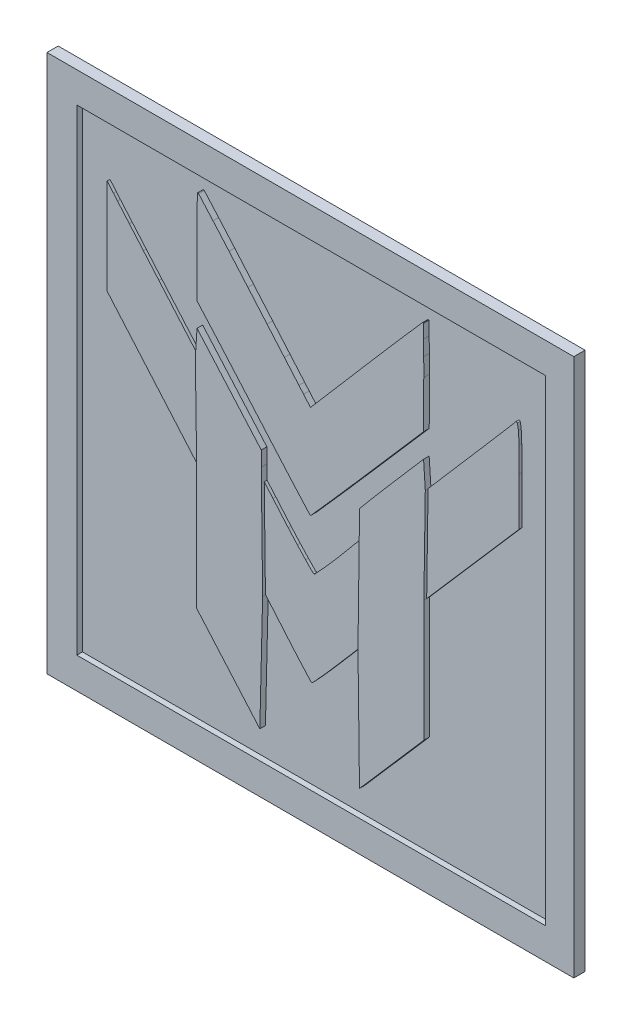
SolidWorks part; units mm, degrees
ref_plane "Front Plane" through (0, 0, 0) normal (0, 0, 1) x (1, 0, 0)
ref_plane "Top Plane" through (0, 0, 0) normal (0, 1, 0) x (1, 0, 0)
ref_plane "Right Plane" through (0, 0, 0) normal (1, 0, 0) x (0, 0, -1)
sketch "Model" plane through (0, 0, 0) normal (0, 0, 1) x (1, 0, 0)
  line L0 (33.0408, 138.25) -> (33.0816, 121.5)
  line L1 (33.0816, 121.5) -> (37.9485, 116)
  line L2 (37.9485, 116) -> (40.7262, 112.8407)
  line L3 (40.7262, 112.8407) -> (45.8443, 106.975)
  line L4 (45.8443, 106.975) -> (51.8256, 100.1032)
  line L5 (51.8256, 100.1032) -> (57.9935, 93)
  line L6 (57.9935, 93) -> (63.8389, 86.2903)
  line L7 (68.8187, 80.6406) -> (73.2898, 75.6085)
  line L8 (73.7744, 75.6093) -> (79.664, 82.2562)
  line L9 (86.2039, 89.6813) -> (93.9024, 98.5)
  line L10 (93.9024, 98.5) -> (113.9132, 121.5)
  line L11 (113.9132, 121.5) -> (113.9566, 138.25)
  line L12 (113.8851, 150.0797) -> (113.7941, 154.8608)
  line L13 (113.4179, 154.8938) -> (107.5701, 148.2145)
  line L14 (101.079, 140.7574) -> (93.4361, 131.9005)
  line L15 (93.4361, 131.9005) -> (73.5679, 108.801)
  line L16 (73.5679, 108.801) -> (71.1065, 111.6505)
  line L17 (71.1065, 111.6505) -> (69.44, 113.5836)
  line L18 (69.44, 113.5836) -> (64.254, 119.6114)
  line L19 (64.254, 119.6114) -> (58.0834, 126.7856)
  line L20 (58.0834, 126.7856) -> (51.2352, 134.75)
  line L21 (51.2352, 134.75) -> (44.5303, 142.5141)
  line L22 (38.8182, 149.0516) -> (33.6892, 154.8751)
  line L23 (33.2445, 154.8359) -> (33.1332, 150.0797)
  line L24 (0.036, 124.5) -> (0.0001, 107.5)
  line L25 (0.0001, 107.5) -> (16.5, 88.3599)
  line L26 (16.5, 88.3599) -> (33, 69.2198)
  line L27 (33, 69.2198) -> (33, 47.8254)
  line L28 (33, 47.8254) -> (33, 26.431)
  line L29 (33, 26.431) -> (44.25, 13.4785)
  line L30 (44.25, 13.4785) -> (55.5, 0.5261)
  line L31 (55.5, 0.5261) -> (56, 21.2648)
  line L32 (56, 21.2648) -> (56.5, 42.0036)
  line L33 (56.5, 42.0036) -> (64.5, 32.5666)
  line L34 (70.2969, 25.8917) -> (72.6749, 23.2531)
  line L35 (73.3274, 23.2256) -> (75.85, 25.9702)
  line L36 (82, 32.9302) -> (90.5, 42.7993)
  line L37 (90.5, 42.7993) -> (90.7697, 21.3399)
  line L38 (90.7697, 21.3399) -> (91.0393, -0.1195)
  line L39 (91.0393, -0.1195) -> (102.5197, 13.0656)
  line L40 (102.5197, 13.0656) -> (114, 26.2506)
  line L41 (114, 26.2506) -> (114.0006, 47.8753)
  line L42 (114.0006, 47.8753) -> (114.0013, 69.5)
  line L43 (114.0013, 69.5) -> (130.5006, 88.4566)
  line L44 (130.5006, 88.4566) -> (147, 107.4132)
  line L45 (147, 107.4132) -> (146.9682, 124.4566)
  line L46 (144.8065, 138.8353) -> (140.4516, 133.7563)
  line L47 (140.4516, 133.7563) -> (135.336, 127.8101)
  line L48 (135.336, 127.8101) -> (129.5, 121.0523)
  line L49 (129.5, 121.0523) -> (114.5, 103.71)
  line L50 (114.5, 103.71) -> (114.1956, 108.3444)
  line L51 (114.1956, 108.3444) -> (113.8913, 112.9787)
  line L52 (113.8913, 112.9787) -> (102.4514, 99.7394)
  line L53 (76.7235, 59.9622) -> (74.2571, 57.2865)
  line L54 (73.382, 57.2298) -> (70.829, 59.8845)
  line L55 (95.0771, 91.1037) -> (91.0033, 86.2762)
  line L56 (33.1107, 113.0274) -> (32.8053, 108.4215)
  line L57 (32.8053, 108.4215) -> (32.5, 103.8157)
  line L58 (32.5, 103.8157) -> (18.5, 120.0291)
  line L59 (18.5, 120.0291) -> (12.9763, 126.4308)
  line L60 (12.9763, 126.4308) -> (7.9621, 132.252)
  line L61 (7.9621, 132.252) -> (3.7607, 137.1379)
  line L62 (3.7607, 137.1379) -> (2.286, 138.8713)
  line L63 (2.286, 138.8713) -> (0.0719, 141.5)
  line L64 (0.0719, 141.5) -> (0.036, 124.5)
  line L65 (33, 69.2198) -> (32.5, 103.8157)
  line L66 (56.5, 42.0036) -> (56.014, 81.5865)
  line L67 (90.5, 42.7993) -> (91.0033, 81.5)
  line L68 (114.0013, 69.5) -> (114.5, 103.71)
  line L69 (33.1107, 113.0274) -> (56.014, 86.8827)
  line L70 (56.014, 86.8827) -> (56.014, 81.5865)
  line L71 (32.5, 103.8157) -> (59.1934, 73.0087) construction
  line L72 (59.1934, 73.0087) -> (56.0752, 76.6075)
  line L73 (91.0033, 86.2762) -> (91.0033, 81.5)
  line L74 (114.5, 103.71) -> (87.8675, 72.9491) construction
  line L75 (87.8675, 72.9491) -> (90.9382, 76.4959)
  line L77 (-20.401, -20.4475) -> (167.4641, -20.4475)
  line L78 (-20.401, -20.4475) -> (-20.401, 171.4475)
  line L79 (-20.401, 171.4475) -> (167.4641, 171.4475)
  line L80 (167.4641, -20.4475) -> (167.4641, 171.4475)
  line L81 (-20.401, -20.4475) -> (167.4641, 171.4475) construction
  line L82 (-20.401, 171.4475) -> (167.4641, -20.4475) construction
  line L83 (157.3002, -9.3509) -> (-9.7514, -9.3509)
  line L84 (157.3002, -9.3509) -> (157.3002, 160.5695)
  line L85 (157.3002, 160.5695) -> (-9.7514, 160.5695)
  line L86 (-9.7514, -9.3509) -> (-9.7514, 160.5695)
  line L87 (157.3002, -9.3509) -> (-9.7514, 160.5695) construction
  line L88 (157.3002, 160.5695) -> (-9.7514, -9.3509) construction
  arc A0 (63.8389, 86.2903) -> (68.8187, 80.6406) centre (848.3924, 772.8169) ccw
  arc A1 (73.2898, 75.6085) -> (73.5315, 75.5) centre (73.5315, 75.8234) ccw
  arc A2 (73.5315, 75.5) -> (73.7744, 75.6093) centre (73.5315, 75.8245) ccw
  arc A3 (79.664, 82.2562) -> (86.2039, 89.6813) centre (-1267.0712, 1275.0405) ccw
  arc A4 (113.9566, 138.25) -> (113.9482, 144.6728) centre (-711.1704, 140.3877) ccw
  arc A5 (113.9482, 144.6728) -> (113.8851, 150.0797) centre (-302.5075, 142.5101) ccw
  arc A6 (113.7941, 154.8608) -> (113.6521, 155) centre (113.6521, 154.858) ccw
  arc A7 (113.6521, 155) -> (113.4179, 154.8938) centre (113.6521, 154.6887) ccw
  arc A8 (107.5701, 148.2145) -> (101.079, 140.7574) centre (1498.7, -1069.2639) ccw
  arc A9 (44.5303, 142.5141) -> (38.8182, 149.0516) centre (-864.7896, -646.2386) ccw
  arc A10 (33.6892, 154.8751) -> (33.4126, 155) centre (33.4126, 154.6313) ccw
  arc A11 (33.4126, 155) -> (33.2445, 154.8359) centre (33.4126, 154.8318) ccw
  arc A12 (33.1332, 150.0797) -> (33.0548, 144.6728) centre (384.2786, 142.2843) ccw
  arc A13 (33.0548, 144.6728) -> (33.0408, 138.25) centre (728.4501, 139.9437) ccw
  arc A14 (64.5, 32.5666) -> (67.6028, 28.9465) centre (399.1481, 316.2569) ccw
  arc A15 (67.6028, 28.9465) -> (70.2969, 25.8917) centre (244.8339, 182.531) ccw
  arc A16 (72.6749, 23.2531) -> (73, 23.0954) centre (73.033, 23.5772) ccw
  arc A17 (73, 23.0954) -> (73.3274, 23.2256) centre (73.0279, 23.5021) ccw
  arc A18 (75.85, 25.9702) -> (78.7054, 29.1492) centre (-93.9268, 181.3349) ccw
  arc A19 (78.7054, 29.1492) -> (82, 32.9302) centre (-247.5154, 316.7328) ccw
  arc A20 (146.9682, 124.4566) -> (146.9051, 133.3026) centre (-692.3329, 122.8912) ccw
  arc A21 (146.9051, 133.3026) -> (146.6978, 137.7604) centre (81.3801, 132.4897) ccw
  arc A22 (146.6978, 137.7604) -> (146.323, 139.8287) centre (136.0732, 136.903) ccw
  arc A23 (146.323, 139.8287) -> (145.7182, 139.9472) centre (145.9904, 139.7337) ccw
  arc A24 (144.8065, 138.8353) -> (145.7182, 139.9472) centre (119.4324, 160.5695) ccw
  arc A25 (102.4514, 99.7394) -> (95.0771, 91.1037) centre (837.8575, -535.7132) ccw
  arc A32 (82.7476, 66.8195) -> (87.8675, 72.9491) centre (-228.7014, 332.1676) ccw
  arc A33 (79.5372, 63.1038) -> (82.7476, 66.8195) centre (-187.0176, 296.6536) ccw
  arc A34 (76.7235, 59.9622) -> (79.5372, 63.1038) centre (-66.0018, 190.6222) ccw
  arc A35 (73.8218, 57.0695) -> (74.2571, 57.2865) centre (73.7514, 57.7558) ccw
  arc A36 (73.382, 57.2298) -> (73.8218, 57.0695) centre (73.7671, 57.6031) ccw
  arc A37 (67.9153, 63.0175) -> (70.829, 59.8845) centre (192.1718, 175.6554) ccw
  arc A38 (64.5858, 66.75) -> (67.9153, 63.0175) centre (299.1222, 272.6061) ccw
  arc A39 (59.1934, 73.0087) -> (64.5858, 66.75) centre (402.4744, 363.3201) ccw
extrude "Saliente-Extruir1" add sketch "Model" along normal blind 4 contours L77 L80 L79 L78 L83 L86 L85 L84 region at (-17.7155, 75.5, 0)
extrude "Saliente-Extruir2" add sketch "Model<3>" along normal blind 2 contours L86 L83 L84 L85 A13 A12 L23 A11 A10 L22 A9 L21 L20 L19 L18 L17 L16 L15 L14 A8 L13 A7 A6 L12 A5 A4 L11 L10 L9 A3 L8 A2 A1 L7 A0 L6 L5 L4 L3 L2 L1 L0 L72 A39 A38 A37 L54 A36 A35 region at (73.9621, 71.875, 0)
sketch "Model<3>" plane through (0, 0, 0) normal (0, 0, 1) x (1, 0, 0) same geometry as "Model"
extrude "Saliente-Extruir3" add sketch "Model<4>" along normal blind 4 contours L70 L69 L56 L57 L65 L27 L28 L29 L30 L31 L32 L66 | A12 A13 L0 L1 L2 L3 L4 L5 L6 A0 L7 A1 A2 L8 A3 L9 L10 L11 A4 A5 L12 A6 A7 L13 A8 L14 L15 L16 L17 L18 L19 L20 L21 A9 L22 A10 A11 L23 | L52 A25 L55 L73 L67 L37 L38 L39 L40 L41 L42 L68 L50 L51 region at (34.1748, 141.4589, 0) region at (44.5039, 56.8702, 0) region at (102.4559, 56.4713, 0)
sketch "Model<4>" plane through (0, 0, 0) normal (0, 0, 1) x (1, 0, 0) same geometry as "Model"
extrude "Saliente-Extruir4" add sketch "Model<5>" along normal blind 3 contours L26 L65 L58 L59 L60 L61 L62 L63 L64 L24 L25 | A39 L72 L66 L33 A14 A15 L34 A16 A17 L35 A18 A19 L36 L67 L75 A32 A33 A34 L53 A35 A36 L54 A37 A38 | A24 L46 L47 L48 L49 L68 L43 L44 L45 A20 A21 A22 A23 region at (16.3928, 105.4348, 0) region at (73.3578, 49.5639, 0) region at (130.6015, 105.3811, 0)
sketch "Model<5>" plane through (0, 0, 0) normal (0, 0, 1) x (1, 0, 0) same geometry as "Model"
